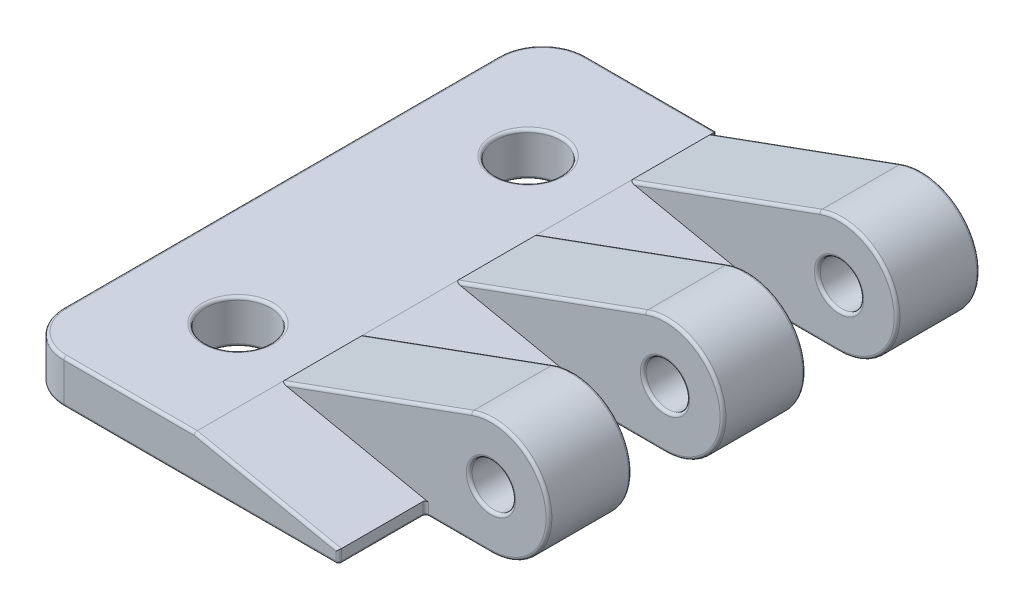
SolidWorks part; units mm, degrees
ref_plane "Front Plane" through (0, 0, 0) normal (0, 0, 1) x (1, 0, 0)
ref_plane "Top Plane" through (0, 0, 0) normal (0, 1, 0) x (1, 0, 0)
ref_plane "Right Plane" through (0, 0, 0) normal (1, 0, 0) x (0, 0, -1)
sketch "Croquis1" plane through (0, 0, 0) normal (0, 0, 1) x (1, 0, 0)
  line L0 (25.0746, 7.7588) -> (12, 3)
  line L2 (0, 0) -> (0, 3)
  line L3 (0, 3) -> (12, 3)
  line L4 (26.4427, 0) -> (0, 0)
  arc A0 (26.4427, 0) -> (25.0746, 7.7588) centre (26.4427, 4) ccw
  circle A1 centre (26.4427, 4) radius 1.5
  point P0 (0, 0)
  point P2 (0, 0)
  point P4 (-8.1, 0)
  point P5 (0, 0)
  dimension "D3" = 3
  dimension "D4" = 4
  dimension "D1" = 3
  dimension "D2" = 12
  dimension "D5" = 20
extrude "Saliente-Extruir1" add sketch "Croquis1" against normal blind 36
sketch "Croquis2" plane through (0, 0, 0) normal (0, 0, 1) x (1, 0, 0)
  line L2 (12, 3) -> (26.4427, 0)
  line L5 (25.0746, 7.7588) -> (12, 3) construction
  line L7 (25.0746, 7.7588) -> (12, 3)
  arc A0 (26.4427, 0) -> (25.0746, 7.7588) centre (26.4427, 4) ccw construction
  arc A2 (26.4427, 0) -> (25.0746, 7.7588) centre (26.4427, 4) ccw
  point P2 (15.1243, 0.0017)
extrude "Cortar-Extruir1" cut sketch "Croquis2" against normal blind 6.3
pattern_linear "MatrizL1" count 3 spacing 12 along (0, 0, -1) of "Cortar-Extruir1"
sketch "Croquis3" plane through (0, 3, 0) normal (0, 1, 0) x (1, 0, 0)
  line L0 (7, 28) -> (7, 8) construction
  line L1 (12, 36) -> (0, 36) construction
  line L3 (0, 36) -> (0, 0) construction
  circle A0 centre (7, 28) radius 2.25
  circle A1 centre (7, 8) radius 2.25
  dimension "D1" = 4.5
  dimension "D2" = 4.5
  dimension "D3" = 20
  dimension "D4" = 8
  dimension "D5" = 7
extrude "Cortar-Extruir2" cut sketch "Croquis3" against normal through all
fillet "Redondeo1" radius 3 2 edges at (0, 1.5, 0) (0, 1.5, -36)
ref_axis "Assi1" through (26.4427, 4, -52.309) along (0, 0, 1)
chamfer "Smusso1" [suppressed] distance 3 angle 45
fillet "Raccordo2" [suppressed] radius 0.5
sketch "Schizzo1" plane through (0, 0, -6.3) normal (0, 0, 1) x (1, 0, 0)
  line L0 (4.75, 3) -> (9.25, 3) construction
  point P0 (26.4427, 4)
sketch "Schizzo2" plane through (0, 0, -6.3) normal (0, 0, 1) x (1, 0, 0)
  line L2 (25.0746, 7.7588) -> (12, 3)
  line L3 (12, 3) -> (26.4427, 0)
  line L4 (25.0746, 7.7588) -> (12, 3)
  line L5 (12, 3) -> (26.4427, 0)
  arc A1 (26.4427, 0) -> (25.0746, 7.7588) centre (26.4427, 4) ccw
  arc A2 (26.4427, 0) -> (25.0746, 7.7588) centre (26.4427, 4) ccw
  dimension "D1" = 0
extrude "Estrusione-Estrusione1" add sketch "Schizzo2" along normal blind 0.3
sketch "Schizzo3" plane through (0, 0, -18.3) normal (0, 0, 1) x (1, 0, 0)
  line L2 (25.0746, 7.7588) -> (12, 3)
  line L3 (12, 3) -> (26.4427, 0)
  line L4 (25.0746, 7.7588) -> (12, 3)
  line L5 (12, 3) -> (26.4427, 0)
  arc A1 (26.4427, 0) -> (25.0746, 7.7588) centre (26.4427, 4) ccw
  arc A2 (26.4427, 0) -> (25.0746, 7.7588) centre (26.4427, 4) ccw
  dimension "D1" = 0
extrude "Estrusione-Estrusione2" add sketch "Schizzo3" along normal blind 0.3
sketch "Schizzo4" plane through (0, 0, -30.3) normal (0, 0, 1) x (1, 0, 0)
  line L2 (25.0746, 7.7588) -> (12, 3)
  line L3 (12, 3) -> (26.4427, 0)
  line L4 (25.0746, 7.7588) -> (12, 3)
  line L5 (12, 3) -> (26.4427, 0)
  arc A1 (26.4427, 0) -> (25.0746, 7.7588) centre (26.4427, 4) ccw
  arc A2 (26.4427, 0) -> (25.0746, 7.7588) centre (26.4427, 4) ccw
  dimension "D1" = 0
extrude "Estrusione-Estrusione3" add sketch "Schizzo4" along normal blind 0.3
sketch "Schizzo5" plane through (0, 0, -36) normal (0, 0, -1) x (-1, 0, 0)
  line L0 (-12, 3) -> (-12, 0)
  line L2 (-26.4427, 0) -> (-3, 0)
  line L3 (-12, 3) -> (-25.0746, 7.7588)
  line L4 (-26.4427, 0) -> (-12, 0)
  line L5 (-12, 3) -> (-25.0746, 7.7588)
  line L8 (-3, 0) -> (-3, 3)
  line L10 (-3, 3) -> (-12, 3)
  arc A1 (-25.0746, 7.7588) -> (-26.4427, 0) centre (-26.4427, 4) ccw
  arc A2 (-25.0746, 7.7588) -> (-26.4427, 0) centre (-26.4427, 4) ccw
  dimension "D1" = 0
extrude "Taglio-Estrusione1" cut sketch "Schizzo5" against normal blind 0.3
sketch "Schizzo6" plane through (0, 0, -24) normal (0, 0, -1) x (-1, 0, 0)
  line L2 (-26.4427, 0) -> (-12, 3)
  line L3 (-12, 3) -> (-25.0746, 7.7588)
  line L4 (-26.4427, 0) -> (-12, 3)
  line L5 (-12, 3) -> (-25.0746, 7.7588)
  arc A1 (-25.0746, 7.7588) -> (-26.4427, 0) centre (-26.4427, 4) ccw
  arc A2 (-25.0746, 7.7588) -> (-26.4427, 0) centre (-26.4427, 4) ccw
  dimension "D1" = 0
extrude "Taglio-Estrusione2" cut sketch "Schizzo6" against normal blind 0.3
sketch "Schizzo7" plane through (0, 0, -12) normal (0, 0, -1) x (-1, 0, 0)
  line L2 (-26.4427, 0) -> (-12, 3)
  line L3 (-12, 3) -> (-25.0746, 7.7588)
  line L4 (-26.4427, 0) -> (-12, 3)
  line L5 (-12, 3) -> (-25.0746, 7.7588)
  arc A1 (-25.0746, 7.7588) -> (-26.4427, 0) centre (-26.4427, 4) ccw
  arc A2 (-25.0746, 7.7588) -> (-26.4427, 0) centre (-26.4427, 4) ccw
  dimension "D1" = 0
extrude "Taglio-Estrusione3" cut sketch "Schizzo7" against normal blind 0.3
sketch "Schizzo8" plane through (0, 0, -30.3) normal (0, 0, -1) x (-1, 0, 0)
  circle A1 centre (-26.4427, 4) radius 1.5
  circle A2 centre (-26.4427, 4) radius 1.5
  dimension "D1" = 0
extrude "Taglio-Estrusione4" cut sketch "Schizzo8" against normal through all both and the other way through all
sketch "Schizzo9" plane through (0, 0, 0) normal (0, -1, 0) x (1, 0, 0)
  line L0 (25.0746, -23.7) -> (30.4427, -23.7) construction
  line L1 (26.4427, 0) -> (21.9427, 0)
  line L2 (26.4427, 0) -> (26.4427, -6)
  line L3 (26.4427, -6) -> (21.9427, -6)
  line L4 (21.9427, 0) -> (21.9427, -6)
  line L5 (26.4427, -18) -> (21.9427, -18)
  line L6 (26.4427, -18) -> (26.4427, -11.7)
  line L7 (26.4427, -11.7) -> (21.9427, -11.7)
  line L8 (21.9427, -18) -> (21.9427, -11.7)
  line L9 (26.4427, -30) -> (21.9427, -30)
  line L10 (26.4427, -30) -> (26.4427, -23.7)
  line L11 (26.4427, -23.7) -> (21.9427, -23.7)
  line L12 (21.9427, -30) -> (21.9427, -23.7)
  line L13 (30.4427, -18) -> (25.0746, -18) construction
  line L14 (25.0746, -11.7) -> (30.4427, -11.7) construction
  line L15 (30.4427, -6) -> (25.0746, -6) construction
  dimension "D1" = 4.5
extrude "Taglio-Estrusione5" cut sketch "Schizzo9" against normal through all both
fillet "Raccordo4" radius 0.2 50 edges at (0, 3, -18) (0.8787, 3, -0.8787) (18.5373, 5.3794, -11.7) (30.3819, 4.6946, -11.7) (18.5373, 5.3794, -18) (30.3819, 4.6946, -18) (18.5373, 5.3794, -23.7) (30.3819, 4.6946, -23.7) (18.5373, 5.3794, -30) (30.3819, 4.6946, -30) (18.5373, 5.3794, -35.7) (30.3819, 4.6946, -35.7) (18.5373, 5.3794, -6) (30.3819, 4.6946, -6) (27.9427, 4, -6) (24.9427, 4, -11.7) (27.9427, 4, -18) (24.9427, 4, -23.7) (27.9427, 4, -30) (24.9427, 4, -35.7) (0.8787, 3, -35.1213) (12, 1.5, -36) (7.5, 3, -36) (7.5, 3, 0) (16.9713, 1.9674, 0) (21.9427, 0.4674, 0) (7, 0, -25.75) (7, 0, -5.75) (24.1927, 0, -11.7) (21.9427, 0, -14.85) (24.1927, 0, -18) (24.1927, 0, -23.7) (21.9427, 0, -26.85) (24.1927, 0, -30) (19.2213, 0, -35.7) (12, 0, -35.85) (7.5, 0, -36) (0.8787, 0, -35.1213) (0, 0, -18) (0.8787, 0, -0.8787) (12.4713, 0, 0) (21.9427, 0, -3) (24.1927, 0, -6) (21.9427, 0.4674, -30) (21.9427, 0.4674, -23.7) (21.9427, 0.4674, -18) (21.9427, 0.4674, -11.7) (21.9427, 0.4674, -6) (7, 3, -5.75) (7, 3, -25.75)
equation "\"num_dents\"= 3"
equation "\"gap\"= .6"
equation "\"llarg\"= 36"
equation "\"D1@Saliente-Extruir1\"=\"llarg\""
equation "\"D1@Cortar-Extruir1\"=(\"llarg\"-\"num_dents\"*\"gap\")/(2*\"num_dents\")+\"gap\""
equation "\"D1@MatrizL1\"=\"num_dents\""
equation "\"D3@MatrizL1\"=\"llarg\"/\"num_dents\""
equation "\"D2@Croquis3\"=\"D1@Croquis3\""
equation "\"D4@Croquis3\"=(\"llarg\"-\"D3@Croquis3\")/2"
